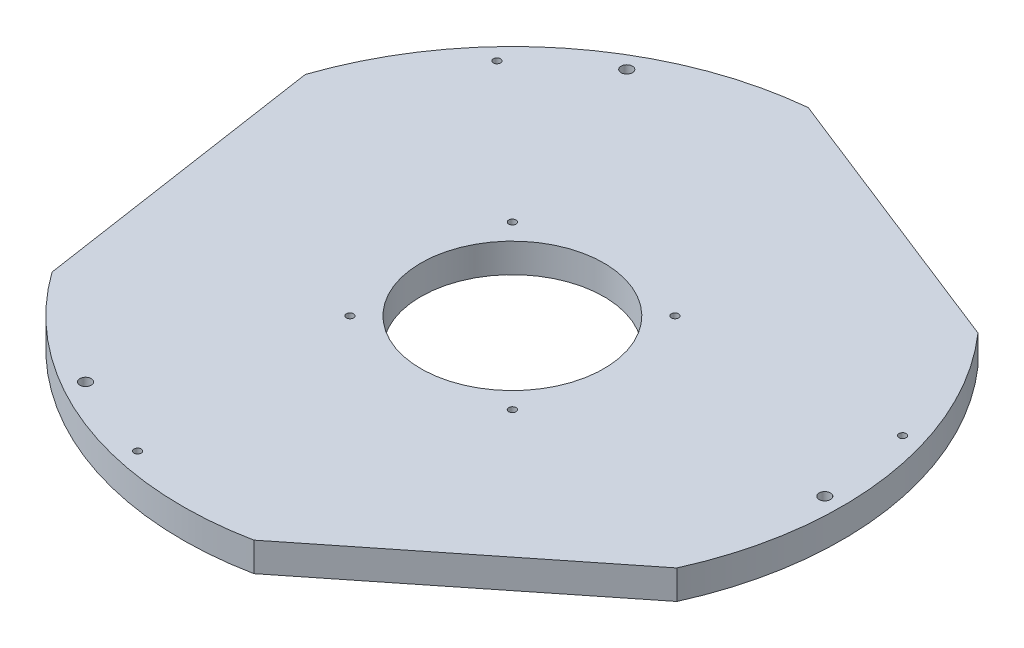
SolidWorks part; units mm, degrees
material "Oak"
ref_plane "Front Plane" through (0, 0, 0) normal (0, 0, 1) x (1, 0, 0)
ref_plane "Top Plane" through (0, 0, 0) normal (0, 1, 0) x (1, 0, 0)
ref_plane "Right Plane" through (0, 0, 0) normal (1, 0, 0) x (0, 0, -1)
sketch "Sketch1" plane through (0, 0, 0) normal (0, 0, 1) x (1, 0, 0)
  line L0 (0, -200000) -> (0, 218797.9879) construction
  line L1 (144.145, -24.4122) -> (144.145, -37.1122) construction
  line L2 (0, -24.4122) -> (144.145, -24.4122) construction
  line L3 (144.145, -37.1122) -> (0, -37.1122) construction
  line L4 (0, -200000) -> (0, 218797.9879) construction
  line L5 (144.145, -24.4122) -> (144.145, -37.1122)
  line L6 (0, -24.4122) -> (144.145, -24.4122)
  line L7 (144.145, -37.1122) -> (0, -37.1122)
  line L8 (0, -24.4122) -> (0, -37.1122)
revolve "Revolve1" add sketch "Sketch1" angle 360 about L4
hole_wizard "1/8 (0.125) Diameter Hole1" positions "Sketch2" profile "Sketch3" hole size "1/8" standard "ANSI Inch" end condition up to next
sketch "Sketch2" plane through (0, -24.4122, 0) normal (0, 1, 0) x (1, 0, 0)
  line L0 (0, 0) -> (136.525, 0) construction
  line L3 (0, 0) -> (-68.2625, -118.2341) construction
  line L6 (0, 0) -> (-68.2625, 118.2341) construction
  line L7 (-99.8481, 93.1098) -> (0, 0) construction
  line L9 (0, 0) -> (-30.7114, -133.0259) construction
  line L12 (0, 0) -> (130.5595, 39.916) construction
  line L14 (-35.5, -35.5) -> (35.5, -35.5) construction
  line L15 (-35.5, -35.5) -> (-35.5, 35.5) construction
  line L16 (-35.5, 35.5) -> (35.5, 35.5) construction
  line L17 (35.5, -35.5) -> (35.5, 35.5) construction
  line L18 (-35.5, 0) -> (0, 0) construction
  line L19 (0, 0) -> (0, -35.5) construction
  circle A0 centre (0, 0) radius 136.525
  point P0 (136.525, 0)
  point P2 (-68.2625, -118.2341)
  point P4 (-68.2625, 118.2341)
  point P32 (-99.8481, 93.1098)
  point P57 (130.5595, 39.916)
  point P60 (-30.7114, -133.0259)
  point P138 (-35.5, -35.5)
  point P141 (-35.5, 35.5)
  point P144 (35.5, 35.5)
  point P147 (35.5, -35.5)
  dimension "D3" = 17
  dimension "D1" = 120
  dimension "D2" = 120
  dimension "D4" = 120
  dimension "D5" = 120
  dimension "D6" = 71
sketch "Sketch3" plane through (136.525, -24.4122, 0) normal (1, 0, 0) x (0, 0, 1)
  line L0 (0, 0) -> (0, 12.7)
  line L1 (0, 12.7) -> (1.5875, 12.7)
  line L2 (1.5875, 12.7) -> (1.5875, 0)
  line L5 (1.5875, 0) -> (0, 0)
  line L11 (0, -6.35) -> (0, 107.95) construction
  dimension "Thru Hole Dia." = 3.175
  dimension "Thru Hole Depth" = 12.7
sketch "Sketch4" plane through (0, -24.4122, 0) normal (0, 1, 0) x (1, 0, 0)
  line L0 (253.7221, 37.919) -> (-94.0222, -238.6893)
  line L1 (-94.0222, -238.6893) -> (-159.6999, 200.7703)
  line L2 (-159.6999, 200.7703) -> (253.7221, 37.919)
  line L3 (253.7221, 37.919) -> (0, 0) construction
  line L4 (130.5595, 39.916) -> (136.525, 0) construction
  circle A0 centre (0, 0) radius 128.27 construction
  point P6 (133.5423, 19.958)
  dimension "D1" = 256.54
extrude "Cut-Extrude1" cut sketch "Sketch4" against normal through all flip side to cut
sketch "Sketch6" plane through (0, -24.4122, 0) normal (0, 1, 0) x (1, 0, 0)
  circle A0 centre (0, 0) radius 40
  dimension "D1" = 80
extrude "Cut-Extrude2" cut sketch "Sketch6" against normal through all
hole_wizard "M6x1.0 Tapped Hole1" positions "Sketch7" profile "Sketch8" tap size "M6x1.0" standard "ANSI Metric" end condition through all
sketch "Sketch7" plane through (0, -24.4122, 0) normal (0, 1, 0) x (1, 0, 0)
  point P0 (-68.2625, 118.2341)
  point P4 (136.525, 0)
  point P8 (-68.2625, -118.2341)
sketch "Sketch8" plane through (-68.2625, -24.4122, -118.2341) normal (1, 0, 0) x (0, 0, 1)
  line L0 (0, 0) -> (0, 12.7)
  line L1 (0, 12.7) -> (2.5, 12.7)
  line L2 (2.5, 12.7) -> (2.5, 0)
  line L5 (2.5, 0) -> (0, 0)
  line L11 (0, -6.35) -> (0, 107.95) construction
  dimension "Thru Tap Drill Dia." = 5
  dimension "Thru Tap Drill Depth" = 12.7
cosmetic thread "Hole Thread1" parameters "D2"=6
cosmetic thread "Hole Thread2" parameters "D2"=6
cosmetic thread "Hole Thread3" parameters "D2"=6
